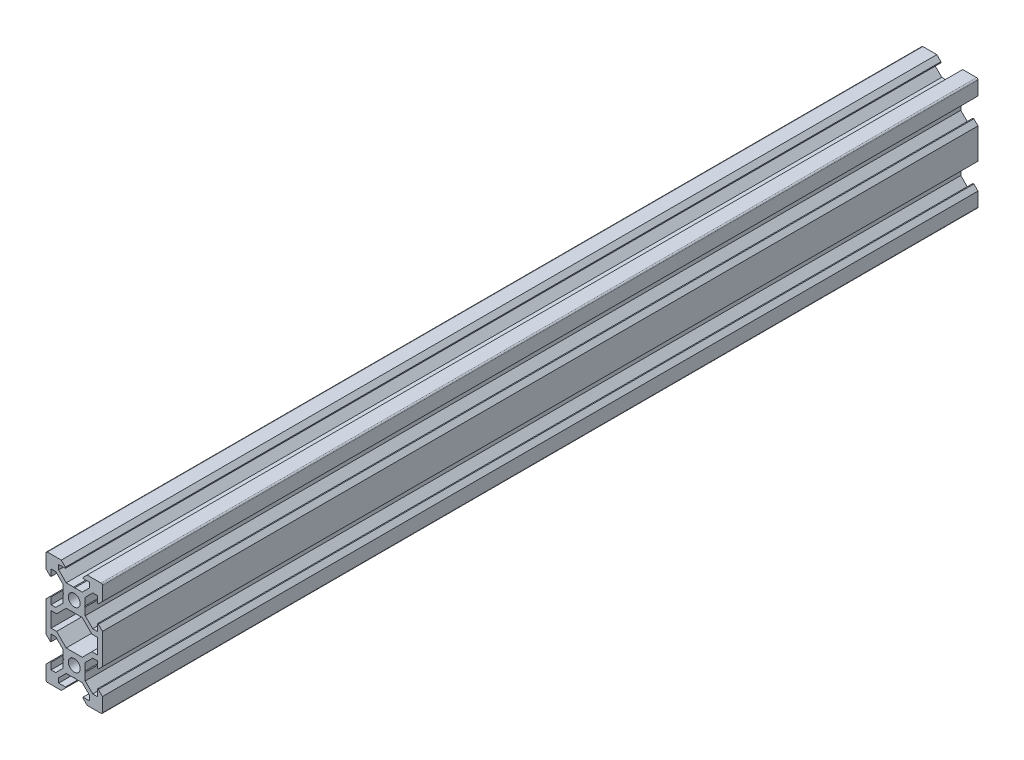
SolidWorks part; units mm, degrees
material "6061-T6 (SS)"
ref_plane "Front Plane" through (0, 0, 0) normal (0, 0, 1) x (1, 0, 0)
ref_plane "Top Plane" through (0, 0, 0) normal (0, 1, 0) x (1, 0, 0)
ref_plane "Right Plane" through (0, 0, 0) normal (1, 0, 0) x (0, 0, -1)
sketch "Sketch1" plane through (0, 0, 0) normal (0, 0, 1) x (1, 0, 0)
  line L0 (0, 0) -> (10, 0) construction
  line L1 (9.5, -20) -> (-9.5, -20)
  line L2 (10, -19.5) -> (10, 19.5)
  line L3 (9.5, 20) -> (-9.5, 20)
  line L4 (-10, -19.5) -> (-10, 19.5)
  line L5 (10, -20) -> (-10, 20) construction
  line L6 (10, 20) -> (-10, -20) construction
  circle A0 centre (0, 10) radius 2.1
  circle A1 centre (0, -10) radius 2.1
  arc A2 (-9.5, -20) -> (-10, -19.5) centre (-9.5, -19.5) cw
  arc A3 (9.5, -20) -> (10, -19.5) centre (9.5, -19.5) ccw
  arc A4 (10, 19.5) -> (9.5, 20) centre (9.5, 19.5) ccw
  arc A5 (-9.5, 20) -> (-10, 19.5) centre (-9.5, 19.5) ccw
  point P0 (0, 0)
  line B0 (0, 10) -> (0, 20) construction
  line B1 (0, 13.69) -> (-0.21, 13.9)
  line B2 (-0.21, 13.9) -> (-2.8393, 13.9)
  line B3 (-2.8393, 13.9) -> (-5.5, 16.5607)
  line B4 (-5.5, 16.5607) -> (-5.5, 18.2)
  line B5 (-5.5, 18.2) -> (-3.125, 18.2)
  line B6 (-3.125, 18.2) -> (-3.125, 18.545)
  line B7 (-3.125, 18.545) -> (-4.58, 20)
  line B8 (-4.58, 20) -> (4.58, 20)
  line B9 (0, 10) -> (-5.9132, 15.9132) construction
  line B10 (3.125, 18.545) -> (4.58, 20)
  line B11 (3.125, 18.2) -> (3.125, 18.545)
  line B12 (5.5, 18.2) -> (3.125, 18.2)
  line B13 (5.5, 16.5607) -> (5.5, 18.2)
  line B14 (2.8393, 13.9) -> (5.5, 16.5607)
  line B15 (0.21, 13.9) -> (2.8393, 13.9)
  line B16 (0, 13.69) -> (0.21, 13.9)
  line B17 (0, 10) -> (-10, 10) construction
  line B18 (-3.69, 10) -> (-3.9, 9.79)
  line B19 (-3.9, 9.79) -> (-3.9, 7.1607)
  line B20 (-3.9, 7.1607) -> (-6.5607, 4.5)
  line B21 (-6.5607, 4.5) -> (-8.2, 4.5)
  line B22 (-8.2, 4.5) -> (-8.2, 6.875)
  line B23 (-8.2, 6.875) -> (-8.545, 6.875)
  line B24 (-8.545, 6.875) -> (-10, 5.42)
  line B25 (-10, 5.42) -> (-10, 14.58)
  line B26 (0, 10) -> (-5.9132, 4.0868) construction
  line B27 (-8.545, 13.125) -> (-10, 14.58)
  line B28 (-8.2, 13.125) -> (-8.545, 13.125)
  line B29 (-8.2, 15.5) -> (-8.2, 13.125)
  line B30 (-6.5607, 15.5) -> (-8.2, 15.5)
  line B31 (-3.9, 12.8393) -> (-6.5607, 15.5)
  line B32 (-3.9, 10.21) -> (-3.9, 12.8393)
  line B33 (-3.69, 10) -> (-3.9, 10.21)
  line B34 (0, -10) -> (-10, -10) construction
  line B35 (-3.69, -10) -> (-3.9, -10.21)
  line B36 (-3.9, -10.21) -> (-3.9, -12.8393)
  line B37 (-3.9, -12.8393) -> (-6.5607, -15.5)
  line B38 (-6.5607, -15.5) -> (-8.2, -15.5)
  line B39 (-8.2, -15.5) -> (-8.2, -13.125)
  line B40 (-8.2, -13.125) -> (-8.545, -13.125)
  line B41 (-8.545, -13.125) -> (-10, -14.58)
  line B42 (-10, -14.58) -> (-10, -5.42)
  line B43 (0, -10) -> (-5.9132, -15.9132) construction
  line B44 (-8.545, -6.875) -> (-10, -5.42)
  line B45 (-8.2, -6.875) -> (-8.545, -6.875)
  line B46 (-8.2, -4.5) -> (-8.2, -6.875)
  line B47 (-6.5607, -4.5) -> (-8.2, -4.5)
  line B48 (-3.9, -7.1607) -> (-6.5607, -4.5)
  line B49 (-3.9, -9.79) -> (-3.9, -7.1607)
  line B50 (-3.69, -10) -> (-3.9, -9.79)
  line B51 (0, -10) -> (0, -20) construction
  line B52 (0, -13.69) -> (0.21, -13.9)
  line B53 (0.21, -13.9) -> (2.8393, -13.9)
  line B54 (2.8393, -13.9) -> (5.5, -16.5607)
  line B55 (5.5, -16.5607) -> (5.5, -18.2)
  line B56 (5.5, -18.2) -> (3.125, -18.2)
  line B57 (3.125, -18.2) -> (3.125, -18.545)
  line B58 (3.125, -18.545) -> (4.58, -20)
  line B59 (4.58, -20) -> (-4.58, -20)
  line B60 (0, -10) -> (5.9132, -15.9132) construction
  line B61 (-3.125, -18.545) -> (-4.58, -20)
  line B62 (-3.125, -18.2) -> (-3.125, -18.545)
  line B63 (-5.5, -18.2) -> (-3.125, -18.2)
  line B64 (-5.5, -16.5607) -> (-5.5, -18.2)
  line B65 (-2.8393, -13.9) -> (-5.5, -16.5607)
  line B66 (-0.21, -13.9) -> (-2.8393, -13.9)
  line B67 (0, -13.69) -> (-0.21, -13.9)
  line B68 (0, -10) -> (10, -10) construction
  line B69 (3.69, -10) -> (3.9, -9.79)
  line B70 (3.9, -9.79) -> (3.9, -7.1607)
  line B71 (3.9, -7.1607) -> (6.5607, -4.5)
  line B72 (6.5607, -4.5) -> (8.2, -4.5)
  line B73 (8.2, -4.5) -> (8.2, -6.875)
  line B74 (8.2, -6.875) -> (8.545, -6.875)
  line B75 (8.545, -6.875) -> (10, -5.42)
  line B76 (10, -5.42) -> (10, -14.58)
  line B77 (0, -10) -> (5.9132, -4.0868) construction
  line B78 (8.545, -13.125) -> (10, -14.58)
  line B79 (8.2, -13.125) -> (8.545, -13.125)
  line B80 (8.2, -15.5) -> (8.2, -13.125)
  line B81 (6.5607, -15.5) -> (8.2, -15.5)
  line B82 (3.9, -12.8393) -> (6.5607, -15.5)
  line B83 (3.9, -10.21) -> (3.9, -12.8393)
  line B84 (3.69, -10) -> (3.9, -10.21)
  line B85 (0, 10) -> (10, 10) construction
  line B86 (3.69, 10) -> (3.9, 10.21)
  line B87 (3.9, 10.21) -> (3.9, 12.8393)
  line B88 (3.9, 12.8393) -> (6.5607, 15.5)
  line B89 (6.5607, 15.5) -> (8.2, 15.5)
  line B90 (8.2, 15.5) -> (8.2, 13.125)
  line B91 (8.2, 13.125) -> (8.545, 13.125)
  line B92 (8.545, 13.125) -> (10, 14.58)
  line B93 (10, 14.58) -> (10, 5.42)
  line B94 (0, 10) -> (5.9132, 15.9132) construction
  line B95 (8.545, 6.875) -> (10, 5.42)
  line B96 (8.2, 6.875) -> (8.545, 6.875)
  line B97 (8.2, 4.5) -> (8.2, 6.875)
  line B98 (6.5607, 4.5) -> (8.2, 4.5)
  line B99 (3.9, 7.1607) -> (6.5607, 4.5)
  line B100 (3.9, 9.79) -> (3.9, 7.1607)
  line B101 (3.69, 10) -> (3.9, 9.79)
  line B102 (-8.2, -2.7) -> (-8.2, 2.7)
  line B103 (-8.2, 2.7) -> (-6.2393, 2.7)
  line B104 (-6.2393, 2.7) -> (-2.8393, 6.1)
  line B105 (-2.8393, 6.1) -> (2.8393, 6.1)
  line B106 (0, 6.1) -> (0, 0) construction
  line B107 (0, 0) -> (-8.2, 0) construction
  line B108 (6.2393, 2.7) -> (2.8393, 6.1)
  line B109 (8.2, 2.7) -> (6.2393, 2.7)
  line B110 (8.2, -2.7) -> (8.2, 2.7)
  line B111 (8.2, -2.7) -> (6.2393, -2.7)
  line B112 (6.2393, -2.7) -> (2.8393, -6.1)
  line B113 (-2.8393, -6.1) -> (2.8393, -6.1)
  line B114 (-6.2393, -2.7) -> (-2.8393, -6.1)
  line B115 (-8.2, -2.7) -> (-6.2393, -2.7)
  line B116 (0, 6.1) -> (0, 10) construction
  line B117 (0, 10) -> (-5.0927, 4.9073) construction
  dimension "D4" = 4.2
  dimension "D5" = 0.5
  dimension "D1" = 20
  dimension "D2" = 40
  dimension "D3" = 20
sketch_block_instance "V Slot 1-4"
sketch_block "V Slot 1" parameters "D1"=10, "D2"=11, "D3"=4.3, "D4"=1.8, "D5"=0.21, "D6"=45, "D7"=9.16, "D8"=1.5, "D9"=6.25
sketch_block_instance "V Slot 1-5"
sketch_block_instance "V Slot 1-6"
sketch_block_instance "V Slot 1-7"
sketch_block_instance "V Slot 1-8"
sketch_block_instance "V Slot 1-9"
sketch_block_instance "Center Cutout 1-1"
sketch_block "Center Cutout 1" parameters "D1"=5.4, "D2"=12.2, "D3"=8.2, "D4"=45, "D5"=10, "D6"=1.5
extrude "Boss-Extrude1" add sketch "Sketch1" along normal blind 500 contours B101 B86 B87 B88 B89 B90 B91 B92 L2 A4 L3 B10 B11 B12 B13 B14 B15 B16 B1 B2 B3 B4 B5 B6 B7 A5 L4 B27 B28 B29 B30 B31 B32 B33 B18 B19 B20 B21 B22 B23 B24 B44 B45 B46 B47 B48 B49 B50 B35 region at (7.04, -19.5528, 0)
ref_plane "Upper Plane" through (0, 10, 0) normal (0, 1, 0) x (1, 0, 0)
ref_plane "Lower Plane" through (0, -10, 0) normal (0, 1, 0) x (1, 0, 0)
sketch "Sketch2" plane through (0, 0, 0) normal (0, 0, -1) x (-1, 0, 0)
  line L1 (-40.5279, 20.9489) -> (31.6716, 20.9489)
  line L2 (-40.5279, 20.9489) -> (-40.5279, -37.1058)
  line L3 (-40.5279, -37.1058) -> (31.6716, -37.1058)
  line L4 (31.6716, 20.9489) -> (31.6716, -37.1058)
extrude "Cut-Extrude2" cut sketch "Sketch2" against normal blind 189.7888
